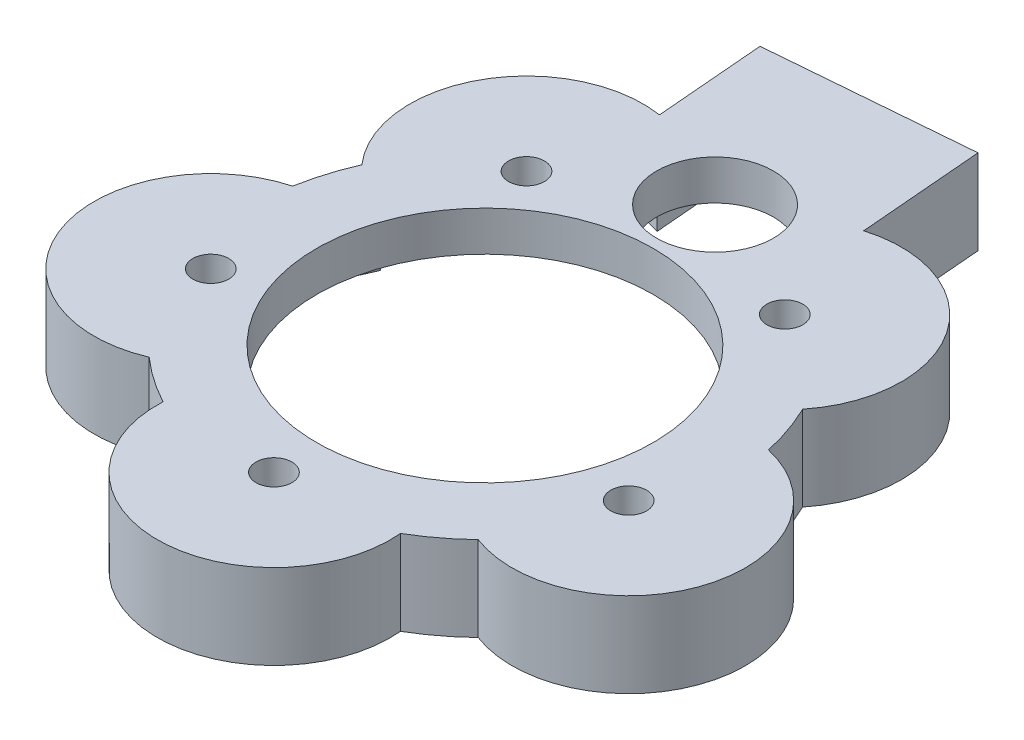
SolidWorks part; units mm, degrees
ref_plane "Front Plane" through (0, 0, 0) normal (0, 0, 1) x (1, 0, 0)
ref_plane "Top Plane" through (0, 0, 0) normal (0, 1, 0) x (1, 0, 0)
ref_plane "Right Plane" through (0, 0, 0) normal (1, 0, 0) x (0, 0, -1)
sketch "Sketch2" plane through (0, -277.7406, 0) normal (0, 1, 0) x (1, 0, 0)
  line L3 (-12.2855, 100.7627) -> (-50.3917, 97.5952)
  line L4 (-12.2855, 100.7627) -> (-50.3917, 97.5952) construction
  line L5 (-50.3917, 97.5952) -> (-48.5145, 75.0118)
  line L6 (-50.3917, 97.5952) -> (-48.5145, 75.0118) construction
  line L7 (-10.1164, 74.6673) -> (-12.2855, 100.7627)
  line L8 (-10.1164, 74.6673) -> (-12.2855, 100.7627) construction
  line L9 (-53.8784, 103.3261) -> (-51.8473, 78.891)
  line L10 (-53.8784, 103.3261) -> (-51.8473, 78.891)
  line L11 (-6.7237, 79.2711) -> (-9.0331, 107.0537)
  line L12 (-6.7237, 79.2711) -> (-9.0331, 107.0537)
  line L13 (-9.0331, 107.0537) -> (-53.8784, 103.3261)
  line L14 (-9.0331, 107.0537) -> (-53.8784, 103.3261)
  circle A0 centre (-55.7838, 53.1908) radius 4
  circle A1 centre (0.6321, 54.3333) radius 4
  circle A4 centre (19.1522, 1.0318) radius 4
  circle A5 centre (-25.8176, -33.053) radius 4
  circle A6 centre (-72.1305, -0.817) radius 4
  circle A7 centre (-25.8176, -33.053) radius 4 construction
  circle A9 centre (-28.3452, 67.7689) radius 13
  arc A10 (-48.5145, 75.0118) -> (-71.8086, 36.6922) centre (-55.7838, 53.1908) ccw
  arc A11 (-71.8086, 36.6922) -> (-76.3165, 21.7989) centre (-26.7895, 14.9372) ccw
  arc A12 (-76.3165, 21.7989) -> (-61.3914, -21.1559) centre (-72.1305, -0.817) ccw
  arc A13 (-61.3914, -21.1559) -> (-48.6201, -30.0453) centre (-26.7895, 14.9372) ccw
  arc A14 (-48.6201, -30.0453) -> (-3.1556, -29.1245) centre (-25.8176, -33.053) ccw
  arc A15 (-3.1556, -29.1245) -> (9.2454, -19.7253) centre (-26.7895, 14.9372) ccw
  arc A16 (9.2454, -19.7253) -> (22.419, 23.7986) centre (19.1522, 1.0318) ccw
  arc A17 (22.419, 23.7986) -> (17.3118, 38.4971) centre (-26.7895, 14.9372) ccw
  arc A18 (17.3118, 38.4971) -> (-10.1164, 74.6673) centre (0.6321, 54.3333) ccw
  arc A20 (-48.5145, 75.0118) -> (-71.8086, 36.6922) centre (-55.7838, 53.1908) ccw construction
  arc A21 (-71.8086, 36.6922) -> (-76.3165, 21.7989) centre (-26.7895, 14.9372) ccw construction
  arc A22 (-76.3165, 21.7989) -> (-61.3914, -21.1559) centre (-72.1305, -0.817) ccw construction
  arc A23 (-61.3914, -21.1559) -> (-48.6201, -30.0453) centre (-26.7895, 14.9372) ccw construction
  arc A24 (-48.6201, -30.0453) -> (-3.1556, -29.1245) centre (-25.8176, -33.053) ccw construction
  arc A25 (-3.1556, -29.1245) -> (9.2454, -19.7253) centre (-26.7895, 14.9372) ccw construction
  arc A26 (9.2454, -19.7253) -> (22.419, 23.7986) centre (19.1522, 1.0318) ccw construction
  arc A27 (22.419, 23.7986) -> (17.3118, 38.4971) centre (-26.7895, 14.9372) ccw construction
  arc A28 (17.3118, 38.4971) -> (-10.1164, 74.6673) centre (0.6321, 54.3333) ccw construction
  circle A30 centre (-26.7895, 14.9372) radius 37.5
  circle A31 centre (-26.7895, 14.9372) radius 37.5 construction
  arc A32 (-75.3798, 36.1029) -> (-78.9614, 24.2697) centre (-26.7895, 14.9372) ccw
  arc A33 (-78.9614, 24.2697) -> (-61.9345, -24.7343) centre (-72.1305, -0.817) ccw
  arc A34 (-61.9345, -24.7343) -> (-51.7872, -31.7973) centre (-26.7895, 14.9372) ccw
  arc A35 (-51.7872, -31.7973) -> (0.0799, -30.7468) centre (-25.8176, -33.053) ccw
  arc A36 (0.0799, -30.7468) -> (9.9329, -23.2788) centre (-26.7895, 14.9372) ccw
  arc A37 (9.9329, -23.2788) -> (24.9617, 26.3744) centre (19.1522, 1.0318) ccw
  arc A38 (24.9617, 26.3744) -> (20.9039, 38.0529) centre (-26.7895, 14.9372) ccw
  arc A39 (20.9039, 38.0529) -> (-6.7237, 79.2711) centre (0.6321, 54.3333) ccw
  arc A41 (-51.8473, 78.891) -> (-75.3798, 36.1029) centre (-55.7838, 53.1908) ccw
  arc A42 (-75.3798, 36.1029) -> (-78.9614, 24.2697) centre (-26.7895, 14.9372) ccw
  arc A43 (-78.9614, 24.2697) -> (-61.9345, -24.7343) centre (-72.1305, -0.817) ccw
  arc A44 (-61.9345, -24.7343) -> (-51.7872, -31.7973) centre (-26.7895, 14.9372) ccw
  arc A45 (-51.7872, -31.7973) -> (0.0799, -30.7468) centre (-25.8176, -33.053) ccw
  arc A46 (0.0799, -30.7468) -> (9.9329, -23.2788) centre (-26.7895, 14.9372) ccw
  arc A47 (9.9329, -23.2788) -> (24.9617, 26.3744) centre (19.1522, 1.0318) ccw
  arc A48 (24.9617, 26.3744) -> (20.9039, 38.0529) centre (-26.7895, 14.9372) ccw
  arc A49 (20.9039, 38.0529) -> (-6.7237, 79.2711) centre (0.6321, 54.3333) ccw
  arc A51 (-51.8473, 78.891) -> (-75.3798, 36.1029) centre (-55.7838, 53.1908) ccw
  dimension "D3" = 26
  dimension "D1" = 0
  dimension "D2" = 0
extrude "Boss-Extrude1" add sketch "Sketch2" along normal up to surface (8.9 mm away)
sketch "Sketch3" plane through (0, -277.7406, 0) normal (0, -1, 0) x (1, 0, 0)
  line L3 (-51.8473, -78.891) -> (-53.8784, -103.3261)
  line L4 (-51.8473, -78.891) -> (-53.8784, -103.3261)
  line L5 (-9.0331, -107.0537) -> (-6.7237, -79.2711)
  line L6 (-9.0331, -107.0537) -> (-6.7237, -79.2711)
  line L7 (-53.8784, -103.3261) -> (-9.0331, -107.0537)
  line L8 (-53.8784, -103.3261) -> (-9.0331, -107.0537)
  line L9 (-50.3917, -97.5952) -> (-12.2855, -100.7627)
  line L10 (-50.3917, -97.5952) -> (-12.2855, -100.7627)
  line L11 (-48.5145, -75.0118) -> (-50.3917, -97.5952)
  line L12 (-48.5145, -75.0118) -> (-50.3917, -97.5952)
  line L13 (-12.2855, -100.7627) -> (-10.1164, -74.6673)
  line L14 (-12.2855, -100.7627) -> (-10.1164, -74.6673)
  arc A10 (-78.9614, -24.2697) -> (-75.3798, -36.1029) centre (-26.7895, -14.9372) ccw
  arc A11 (-61.9345, 24.7343) -> (-78.9614, -24.2697) centre (-72.1305, 0.817) ccw
  arc A12 (-51.7872, 31.7973) -> (-61.9345, 24.7343) centre (-26.7895, -14.9372) ccw
  arc A13 (0.0799, 30.7468) -> (-51.7872, 31.7973) centre (-25.8176, 33.053) ccw
  arc A14 (9.9329, 23.2788) -> (0.0799, 30.7468) centre (-26.7895, -14.9372) ccw
  arc A15 (24.9617, -26.3744) -> (9.9329, 23.2788) centre (19.1522, -1.0318) ccw
  arc A16 (20.9039, -38.0529) -> (24.9617, -26.3744) centre (-26.7895, -14.9372) ccw
  arc A17 (-6.7237, -79.2711) -> (20.9039, -38.0529) centre (0.6321, -54.3333) ccw
  arc A19 (-75.3798, -36.1029) -> (-51.8473, -78.891) centre (-55.7838, -53.1908) ccw
  arc A20 (-78.9614, -24.2697) -> (-75.3798, -36.1029) centre (-26.7895, -14.9372) ccw
  arc A21 (-61.9345, 24.7343) -> (-78.9614, -24.2697) centre (-72.1305, 0.817) ccw
  arc A22 (-51.7872, 31.7973) -> (-61.9345, 24.7343) centre (-26.7895, -14.9372) ccw
  arc A23 (0.0799, 30.7468) -> (-51.7872, 31.7973) centre (-25.8176, 33.053) ccw
  arc A24 (9.9329, 23.2788) -> (0.0799, 30.7468) centre (-26.7895, -14.9372) ccw
  arc A25 (24.9617, -26.3744) -> (9.9329, 23.2788) centre (19.1522, -1.0318) ccw
  arc A26 (20.9039, -38.0529) -> (24.9617, -26.3744) centre (-26.7895, -14.9372) ccw
  arc A27 (-6.7237, -79.2711) -> (20.9039, -38.0529) centre (0.6321, -54.3333) ccw
  arc A29 (-75.3798, -36.1029) -> (-51.8473, -78.891) centre (-55.7838, -53.1908) ccw
  arc A30 (-71.8086, -36.6922) -> (-48.5145, -75.0118) centre (-55.7838, -53.1908) ccw
  arc A31 (-76.3165, -21.7989) -> (-71.8086, -36.6922) centre (-26.7895, -14.9372) ccw
  arc A32 (-61.3914, 21.1559) -> (-76.3165, -21.7989) centre (-72.1305, 0.817) ccw
  arc A33 (-48.6201, 30.0453) -> (-61.3914, 21.1559) centre (-26.7895, -14.9372) ccw
  arc A34 (-3.1556, 29.1245) -> (-48.6201, 30.0453) centre (-25.8176, 33.053) ccw
  arc A35 (9.2454, 19.7253) -> (-3.1556, 29.1245) centre (-26.7895, -14.9372) ccw
  arc A36 (22.419, -23.7986) -> (9.2454, 19.7253) centre (19.1522, -1.0318) ccw
  arc A37 (17.3118, -38.4971) -> (22.419, -23.7986) centre (-26.7895, -14.9372) ccw
  arc A38 (-10.1164, -74.6673) -> (17.3118, -38.4971) centre (0.6321, -54.3333) ccw
  arc A40 (-71.8086, -36.6922) -> (-48.5145, -75.0118) centre (-55.7838, -53.1908) ccw
  arc A41 (-76.3165, -21.7989) -> (-71.8086, -36.6922) centre (-26.7895, -14.9372) ccw
  arc A42 (-61.3914, 21.1559) -> (-76.3165, -21.7989) centre (-72.1305, 0.817) ccw
  arc A43 (-48.6201, 30.0453) -> (-61.3914, 21.1559) centre (-26.7895, -14.9372) ccw
  arc A44 (-3.1556, 29.1245) -> (-48.6201, 30.0453) centre (-25.8176, 33.053) ccw
  arc A45 (9.2454, 19.7253) -> (-3.1556, 29.1245) centre (-26.7895, -14.9372) ccw
  arc A46 (22.419, -23.7986) -> (9.2454, 19.7253) centre (19.1522, -1.0318) ccw
  arc A47 (17.3118, -38.4971) -> (22.419, -23.7986) centre (-26.7895, -14.9372) ccw
  arc A48 (-10.1164, -74.6673) -> (17.3118, -38.4971) centre (0.6321, -54.3333) ccw
  dimension "D1" = 0
  dimension "D2" = 0
extrude "Boss-Extrude2" add sketch "Sketch3" along normal up to surface (10 mm away)
